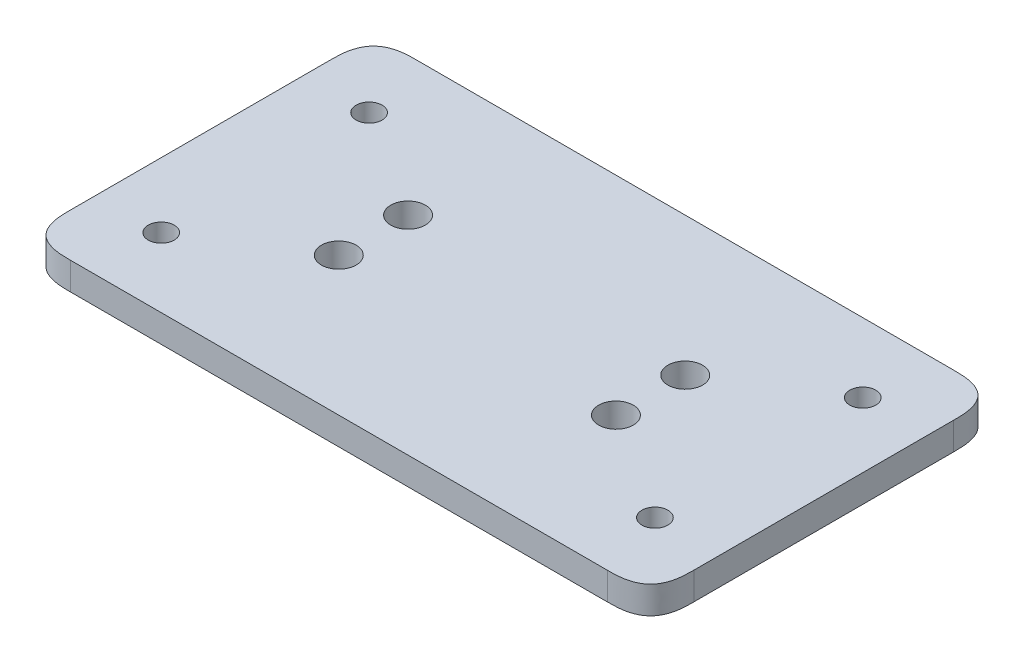
SolidWorks part; units mm, degrees
ref_plane "Front" through (0, 0, 0) normal (0, 0, 1) x (1, 0, 0)
ref_plane "Top" through (0, 0, 0) normal (0, 1, 0) x (1, 0, 0)
ref_plane "Right" through (0, 0, 0) normal (1, 0, 0) x (0, 0, -1)
sketch "Sketch1" plane through (0, 0, 0) normal (0, 1, 0) x (1, 0, 0)
  line L1 (0, 0) -> (72, 0)
  line L2 (0, 0) -> (0, 40)
  line L3 (0, 40) -> (72, 40)
  line L4 (72, 0) -> (72, 40)
  line L5 (72, 24) -> (52, 24)
  line L6 (52, 24) -> (20, 24)
  line L7 (52, 16) -> (20, 16)
  line L9 (36, 40) -> (36, 0)
  circle A0 centre (20, 24) radius 2
  circle A1 centre (20, 16) radius 2
  circle A2 centre (52, 24) radius 2
  circle A3 centre (52, 16) radius 2
  circle A4 centre (7.5, 32) radius 1.5
  circle A5 centre (7.5, 8) radius 1.5
  circle A6 centre (64.5, 8) radius 1.5
  circle A7 centre (64.5, 32) radius 1.5
  point P27 (36, 24)
  dimension "D8" = 8
  dimension "D9" = 24
  dimension "D1" = 72
  dimension "D2" = 40
  dimension "D3" = 36
  dimension "D4" = 24
  dimension "D5" = 8
  dimension "D6" = 32
  dimension "D7" = 0
  dimension "D11" = 0
extrude "Boss-Extrude1" add sketch "Sketch1" along normal blind 3.175 contours A3 L9 L1 L4 L5 A2 L6 A6 | A2 L5 L4 L3 L9 L6 A7 | A1 L9 A0 L3 L2 L1 A5 A4
fillet "Fillet1" radius 5 4 edges at (0, 1.5875, -40) (0, 1.5875, 0) (72, 1.5875, 0) (72, 1.5875, -40) curvature continuous yes
